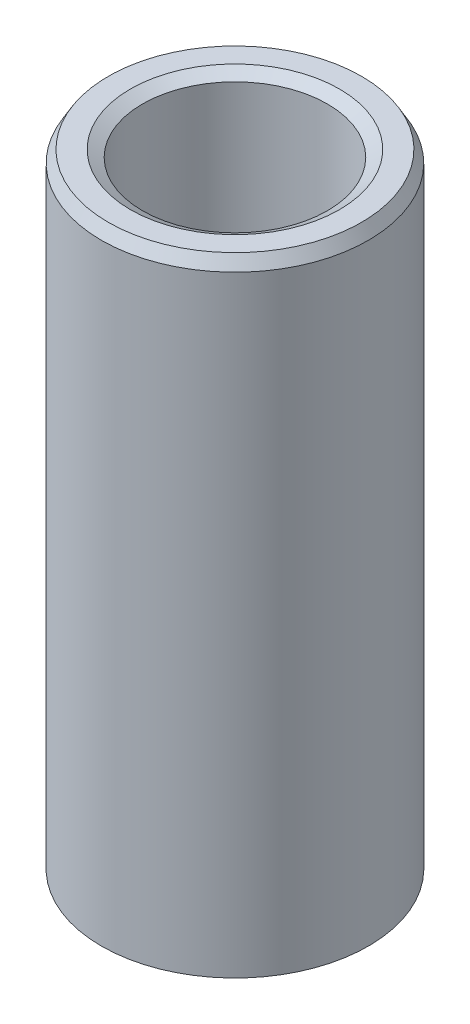
SolidWorks part; units mm, degrees
ref_plane "Front Plane" through (0, 0, 0) normal (0, 0, 1) x (1, 0, 0)
ref_plane "Top Plane" through (0, 0, 0) normal (0, 1, 0) x (1, 0, 0)
ref_plane "Right Plane" through (0, 0, 0) normal (1, 0, 0) x (0, 0, -1)
sketch "Sketch1" plane through (0, 0, 0) normal (0, 1, 0) x (1, 0, 0)
  circle A0 centre (0, 0) radius 15
  dimension "SLEEVE_OD" = 30
extrude "Boss-Extrude1" add sketch "Sketch1" along normal blind 70.8003
sketch "Sketch2" plane through (0, 0, 0) normal (0, 1, 0) x (1, 0, 0)
  circle A0 centre (0, 0) radius 10.3911
  dimension "BORE_D" = 20.7821
extrude "Cut-Extrude1" cut sketch "Sketch2" along normal through all
chamfer "Chamfer1" distance 1.3526 angle 30 4 edges at (0, 70.8003, 10.3911) (0, 0, 10.3911) (0, 0, 15) (0, 70.8003, 15) first distance on face at (0, 70.8003, 10.3911) first distance on face at (0, 0, 10.3911) first distance on face at (0, 70.8003, 15)
